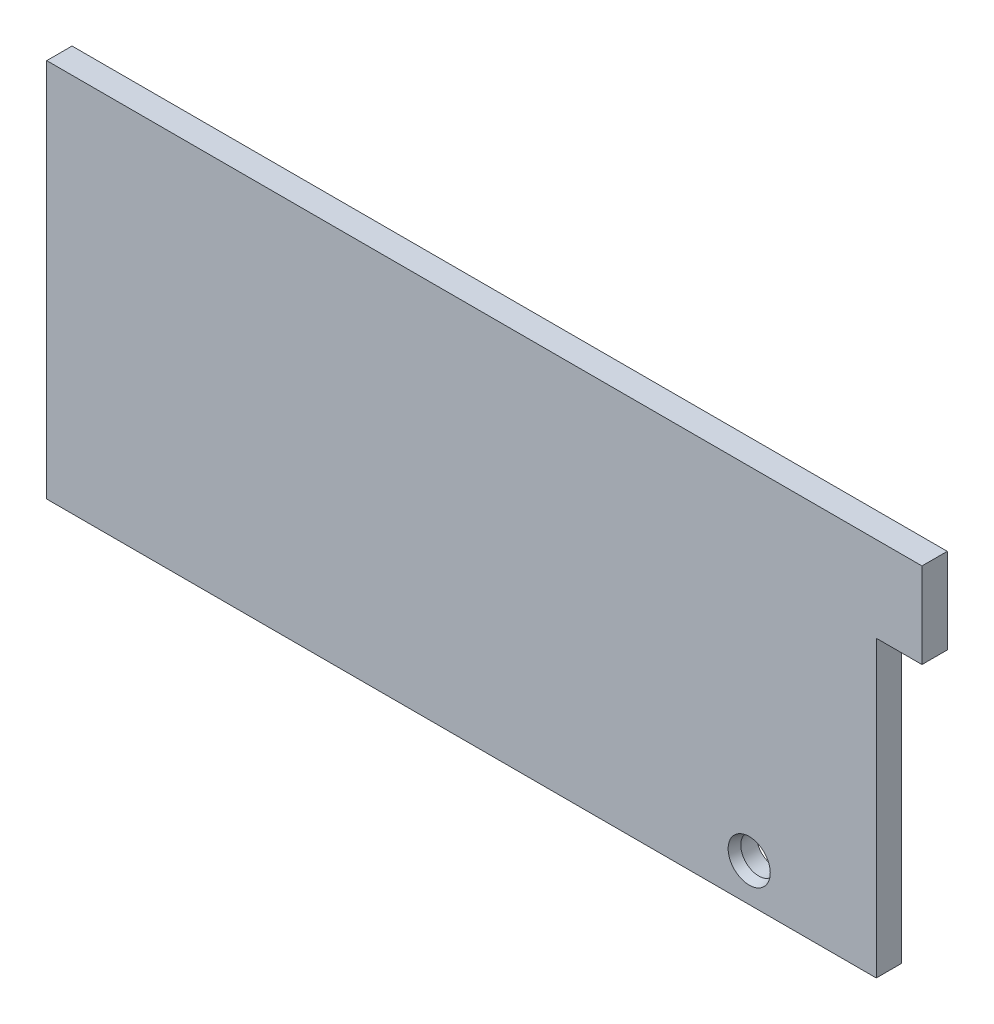
SolidWorks part; units mm, degrees
ref_plane "Front Plane" through (0, 0, 0) normal (0, 0, 1) x (1, 0, 0)
ref_plane "Top Plane" through (0, 0, 0) normal (0, 1, 0) x (1, 0, 0)
ref_plane "Right Plane" through (0, 0, 0) normal (1, 0, 0) x (0, 0, -1)
sketch "Sketch1" plane through (0, 0, 0) normal (0, 0, 1) x (1, 0, 0)
  line L1 (-81, -30) -> (50.0797, -30)
  line L6 (57.3, 16.5) -> (50.0797, 16.5)
  line L11 (57.3, 16.5) -> (57.3, 30)
  line L13 (50.0797, 16.5) -> (50.0797, -30)
  line L18 (57.3, 30) -> (-81, 30)
  line L19 (-81, 30) -> (-81, -30)
  circle A4 centre (-41, 0) radius 5 construction
  circle A5 centre (30, -24) radius 2.83
  point P4 (-81, 0)
  dimension "D5" = 10
  dimension "D9" = 5.66
  dimension "D8" = 13.5
  dimension "D10" = 60
  dimension "D2" = 138.3
  dimension "D3" = 40
  dimension "D4" = 71
  dimension "D6" = 24
extrude "Boss-Extrude1" add sketch "Sketch1" along normal mid plane 4
chamfer "Chamfer1" distance 0.5 distance2 1.5 1 edges at (32.83, -24, 2) first distance on face at (8.7932, 5.5, 2)
equation "\"back_boost\"= 7"
equation "\"D3@Sketch1\"=\"back_boost\"+33.00mm"
equation "\"D2@Sketch1\"=\"back_boost\"+131.30mm"
